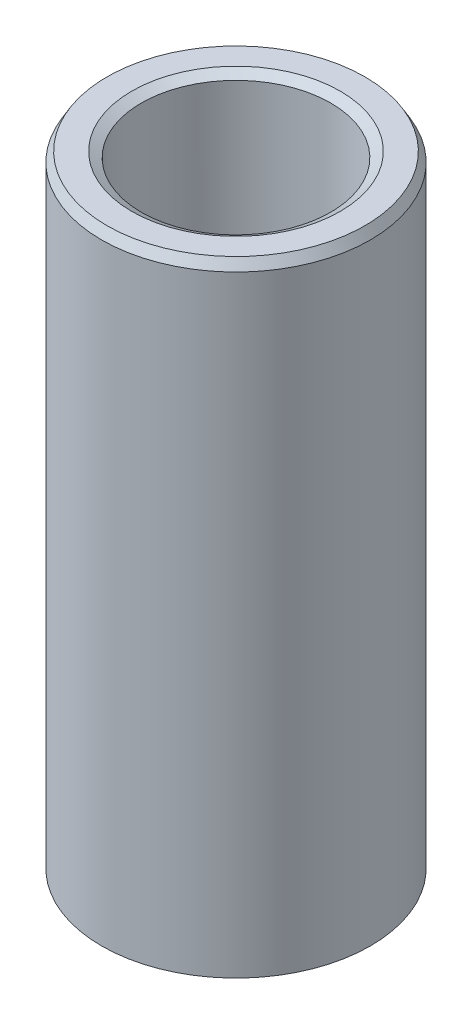
SolidWorks part; units mm, degrees
ref_plane "Front Plane" through (0, 0, 0) normal (0, 0, 1) x (1, 0, 0)
ref_plane "Top Plane" through (0, 0, 0) normal (0, 1, 0) x (1, 0, 0)
ref_plane "Right Plane" through (0, 0, 0) normal (1, 0, 0) x (0, 0, -1)
sketch "Sketch1" plane through (0, 0, 0) normal (0, 1, 0) x (1, 0, 0)
  circle A0 centre (0, 0) radius 52.5
  dimension "SLEEVE_OD" = 105
extrude "Boss-Extrude1" add sketch "Sketch1" along normal blind 244.6145
sketch "Sketch2" plane through (0, 0, 0) normal (0, 1, 0) x (1, 0, 0)
  circle A0 centre (0, 0) radius 36.9667
  dimension "BORE_D" = 73.9334
extrude "Cut-Extrude1" cut sketch "Sketch2" along normal through all
chamfer "Chamfer1" distance 3.7258 angle 30 4 edges at (0, 244.6145, 36.9667) (0, 0, 36.9667) (0, 0, 52.5) (0, 244.6145, 52.5) first distance on face at (0, 244.6145, 36.9667) first distance on face at (0, 0, 36.9667) first distance on face at (0, 244.6145, 52.5)
